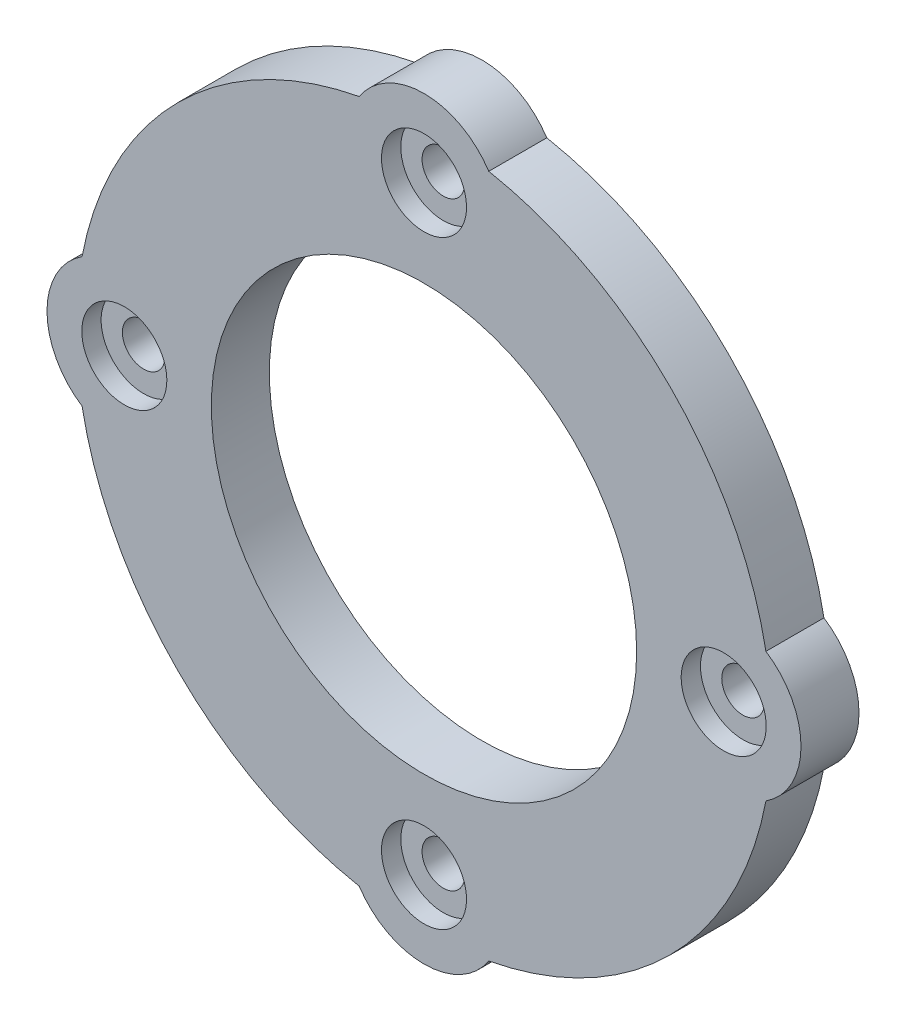
SolidWorks part; units mm, degrees
ref_plane "Спереди" through (0, 0, 0) normal (0, 0, 1) x (1, 0, 0)
ref_plane "Сверху" through (0, 0, 0) normal (0, 1, 0) x (1, 0, 0)
ref_plane "Справа" through (0, 0, 0) normal (1, 0, 0) x (0, 0, -1)
sketch "Эскиз1" plane through (0, 0, 0) normal (0, 0, 1) x (1, 0, 0)
  arc A0 (-17.6855, -3.3502) -> (-3.3502, -17.6855) centre (0, 0) ccw
  circle A1 centre (0, 0) radius 15.5 construction
  arc A2 (-17.6855, 3.3502) -> (-17.6855, -3.3502) centre (-15.5, 0) ccw
  arc A3 (3.3502, 17.6855) -> (-3.3502, 17.6855) centre (0, 15.5) ccw
  arc A4 (17.6855, -3.3502) -> (17.6855, 3.3502) centre (15.5, 0) ccw
  arc A5 (-3.3502, -17.6855) -> (3.3502, -17.6855) centre (0, -15.5) ccw
  arc A6 (-3.3502, 17.6855) -> (-17.6855, 3.3502) centre (0, 0) ccw
  arc A7 (17.6855, 3.3502) -> (3.3502, 17.6855) centre (0, 0) ccw
  arc A8 (3.3502, -17.6855) -> (17.6855, -3.3502) centre (0, 0) ccw
  point P18 (0, 0)
  dimension "D1" = 36
  dimension "D2" = 31
  dimension "D3" = 8
extrude "Бобышка-Вытянуть1" add sketch "Эскиз1" along normal blind 3
sketch "Эскиз2" plane through (0, 0, 3) normal (0, 0, 1) x (1, 0, 0)
  circle A0 centre (0, 0) radius 11
  dimension "D1" = 22
extrude "Вырез-Вытянуть1" cut sketch "Эскиз2" against normal through all
sketch "Эскиз3" plane through (0, 0, 3) normal (0, 0, 1) x (1, 0, 0)
  circle A0 centre (-15.5, 0) radius 2.2
  point P12 (0, 0)
  dimension "D1" = 4.4
  dimension "D2" = 15.5
extrude "Вырез-Вытянуть2" cut sketch "Эскиз3" against normal blind 1 contours A0
sketch "Эскиз4" plane through (0, 0, 2) normal (0, 0, 1) x (1, 0, 0)
  circle A0 centre (-15.5, 0) radius 1.1
  dimension "D1" = 2.2
extrude "Вырез-Вытянуть3" cut sketch "Эскиз4" against normal through all
pattern_circular "Круговой массив1" count 4 over 360 about axis through (0, 0, 3) along (0, 0, -1) of "Вырез-Вытянуть2", "Вырез-Вытянуть3"
